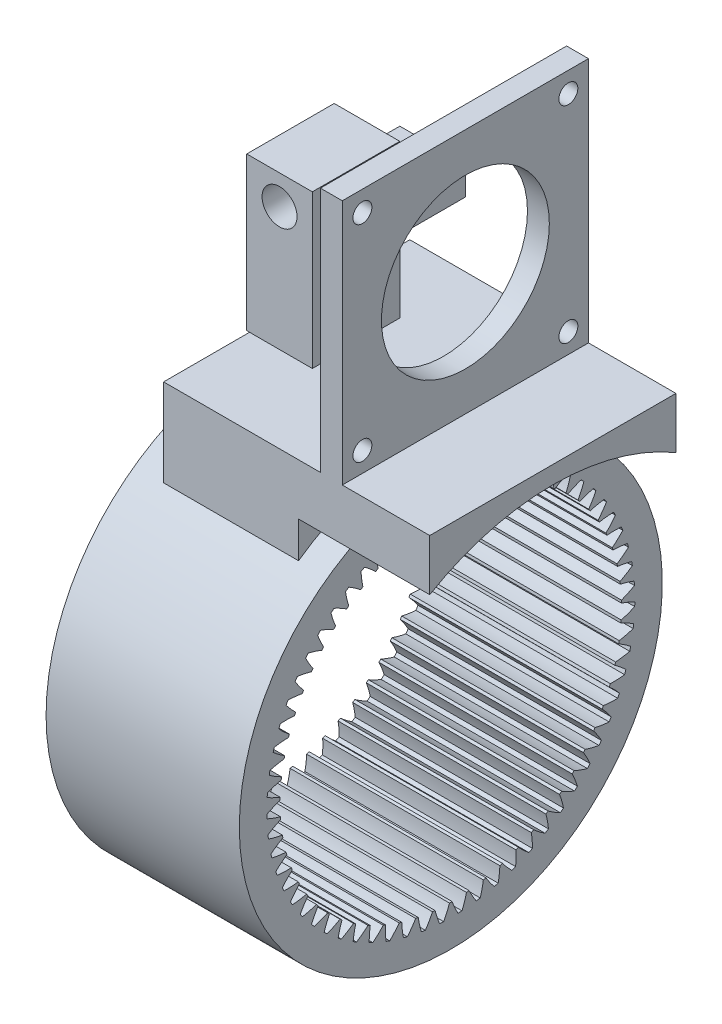
SolidWorks part; units mm, degrees
ref_plane "Plane1" through (0, 0, 0) normal (0, 0, 1) x (1, 0, 0)
ref_plane "Plane2" through (0, 0, 0) normal (0, 1, 0) x (1, 0, 0)
ref_plane "Plane3" through (0, 0, 0) normal (1, 0, 0) x (0, 0, -1)
sketch "HoldingSke" plane through (0, 0, 0) normal (0, 1, 0) x (1, 0, 0)
  line L0 (0, 0) -> (0.5, -0.866)
  line L1 (-15, 0) -> (100, 0) construction
  line L2 (0, 0) -> (-2.1039, 2.3779)
  line L3 (0, 0) -> (-11.863, 4.5341)
  line L4 (0, 0) -> (4.318, 7.479)
  line L5 (0, 0) -> (-23.7986, -8.8762)
  line L6 (0, 0) -> (-10.5278, -7.1032)
  line L7 (-2.1039, 2.3779) -> (3.3635, 27.1825)
  line L8 (-76.2, 3.3779) -> (-54.61, 3.3779)
  line L9 (-71.009, 38.7566) -> (-53.1078, 45.2721)
  line L10 (-76.2, 71.12) -> (104.1128, 71.12)
  line L11 (0, 0) -> (-12, 0)
  line L12 (-76.2, 101.6) -> (-76.162, 101.6)
  line L13 (24.9733, 27.94) -> (52.9518, 28.4284)
  line L14 (24.9733, 27.94) -> (24.9743, 27.94)
  line L15 (24.9733, 27.94) -> (100.4006, 29.5858)
  circle A0 centre (0, 0) radius 12.5
  circle A1 centre (0, 0) radius 12.7
  circle A2 centre (0, 0) radius 12.7
  dimension "MHD" = 25.4
  dimension "Hub_dia" = 25.4
  dimension "Diameter" = 25
  dimension "Num_teeth" = 60
  dimension "Pitch" = 1
  dimension "Overall_len" = 25.4
  dimension "Show_teeth" = 60
  dimension "Thickness" = 12.7
  dimension "OAL" = 25.4001
  dimension "T_dim" = 21.59
  dimension "Ap" = 20
  dimension "H" = 19.05
  dimension "Pitch_radius" = 180.3128
  dimension "Width" = 12
  dimension "Backlash" = 0.038
  dimension "Addendum_fac" = 1
  dimension "Dedendum_fac" = 1.25
  dimension "Clearance_fac" = 0.25
  dimension "Dedendum_add" = 0.001
  dimension "Module" = 1
sketch "BasProSke" plane through (0, 0, 0) normal (0, 1, 0) x (1, 0, 0)
  line L0 (-10, 0) -> (60, 0) construction
  line L1 (0, 29) -> (0, 31.2764)
  line L2 (0, 29) -> (32.815, 29)
  line L3 (32.815, 29) -> (32.815, 31.2764)
  line L4 (32.815, 31.2764) -> (0, 31.2764)
  dimension "Thickness" = 32.815
  dimension "Diameter" = 62.5528
  dimension "Inside_diameter" = 58
revolve "Base-Revolve" add sketch "BasProSke" angle 360 about L0
sketch "TooCutSke" plane through (0, 0, 0) normal (1, 0, 0) x (0, 0, -1)
  line L3 (0.8803, 29.9871) -> (0.8803, 53.6633) construction
  line L4 (0, 0) -> (0, 59.563) construction
  line L5 (0, 0) -> (-3.576, 68.2339) construction
  line L6 (-13.1633, 24.7167) -> (36.4631, 27.3175) construction
  circle A0 centre (0, 0) radius 30 construction
  circle A1 centre (0, 0) radius 31.251 construction
  circle A2 centre (0, 0) radius 25.3717 construction
  circle A3 centre (0, 0) radius 28.9746 construction
  arc A4 (1.2274, 28.9486) -> (0.3395, 31.2492) centre (-13.1633, 24.7167) ccw
  arc A5 (1.2274, 28.9486) -> (-1.2274, 28.9486) centre (0, 0) ccw
  arc A6 (0.3395, 31.2492) -> (-0.3395, 31.2492) centre (0, 0) ccw
  arc A7 (-0.3395, 31.2492) -> (-1.2274, 28.9486) centre (13.1633, 24.7167) ccw
  dimension "Pitch_dia" = 60
  dimension "Base_dia" = 50.7434
  dimension "Root_dia" = 62.502
  dimension "Overcut_dia" = 57.9492
  dimension "Flank_rad" = 15
  dimension "Half_ang" = 3
  dimension "Half_CT" = 0.8803
extrude "ToothCut" cut sketch "TooCutSke" along normal through all
fillet "Breaks" [suppressed] radius 0.1
fillet "RootFillets" [suppressed] radius 0.251
pattern_circular "TeethCuts" count 63 over 360 about axis through (-10, 0, 0) along (1, 0, 0) of "ToothCut"
scale "Scale1" scale about centroid uniform scaling yes scale factor 2
sketch "Sketch1" plane through (49.2225, 0, 0) normal (1, 0, 0) x (0, 0, -1)
  circle A0 centre (0, 0) radius 62.5528
sketch "Sketch2" plane through (49.2225, 0, 0) normal (1, 0, 0) x (0, 0, -1)
  circle A0 centre (0, 0) radius 72.5528
  circle A1 centre (0, 0) radius 62.5528
extrude "Boss-Extrude1" add sketch "Sketch2" against normal blind 65.63
scale "Scale2" scale about centroid uniform scaling yes scale factor 1.1
scale "Scale3" scale about centroid uniform scaling yes scale factor 1.01
scale "Scale4" scale about centroid uniform scaling yes scale factor 0.990099
scale "Scale5" scale about centroid uniform scaling yes scale factor 0.909091
scale "Scale6" scale about centroid uniform scaling yes scale factor 1.01
sketch "Sketch3" plane through (-16.7356, 0, 0) normal (-1, 0, 0) x (0, 0, 1)
  circle A0 centre (0, 0) radius 72.5528
  circle A1 centre (0, 0) radius 73.2783
extrude "Cut-Extrude1" cut sketch "Sketch3" against normal through all
ref_plane "Plane4" through (39.5507, 0, 0) normal (1, 0, 0) x (0, 0, -1)
sketch "Sketch4" plane through (39.5507, 0, 0) normal (1, 0, 0) x (0, 0, -1)
  line L10 (-42.225, 88.9996) -> (-42.225, 58.9996)
  line L11 (42.225, 88.9996) -> (42.225, 58.9996)
  line L12 (0, 0) -> (-42.225, 58.9996) construction
  line L13 (42.225, 58.9996) -> (0, 0) construction
  line L18 (42.225, 88.9996) -> (-42.225, 88.9996)
  arc A0 (42.225, 58.9996) -> (-42.225, 58.9996) centre (0, 0) ccw
  circle A1 centre (0, 0) radius 72.5528 construction
  point P12 (0, 72.5528)
  dimension "D1" = 84.45
  dimension "D3" = 30
extrude "Boss-Extrude2" add sketch "Sketch4" against normal blind 46.2863
scale "Scale7" scale about centroid uniform scaling yes scale factor 0.666667
sketch "Sketch17" plane through (31.8363, 0, 0) normal (1, 0, 0) x (0, 0, -1)
  line L1 (-28.15, 64.6246) -> (-28.15, 44.6246) construction
  line L4 (-28.15, 52.8966) -> (-28.15, 64.6246)
  line L5 (-28.15, 64.6246) -> (28.15, 64.6246)
  line L6 (28.15, 64.6246) -> (28.15, 52.8966)
  arc A1 (28.15, 52.8966) -> (-28.15, 52.8966) centre (0, 5.2915) ccw
  circle A2 centre (0, 5.2915) radius 48.3685 construction
  dimension "D1" = 110.6104
extrude "Boss-Extrude3" add sketch "Sketch17" along normal blind 30
ref_plane "Plane5" through (16.4075, 0, 0) normal (1, 0, 0) x (0, 0, -1)
ref_plane "Plane6" through (41.8363, 0, 0) normal (1, 0, 0) x (0, 0, -1)
sketch "Sketch18" plane through (41.8363, 0, 0) normal (1, 0, 0) x (0, 0, -1)
  line L0 (28.15, 52.8966) -> (28.15, 64.6246) construction
  line L1 (-28.15, 64.6246) -> (28.15, 64.6246)
  line L2 (-28.15, 64.6246) -> (-28.15, 120.9246)
  line L3 (-28.15, 120.9246) -> (28.15, 120.9246)
  line L4 (28.15, 64.6246) -> (28.15, 120.9246)
  line L6 (23.55, 69.1773) -> (-23.55, 69.1773) construction
  line L7 (23.55, 69.1773) -> (23.55, 116.2773) construction
  line L8 (23.55, 116.2773) -> (-23.55, 116.2773) construction
  line L9 (-23.55, 69.1773) -> (-23.55, 116.2773) construction
  line L10 (23.55, 69.1773) -> (-23.55, 116.2773) construction
  line L11 (23.55, 116.2773) -> (-23.55, 69.1773) construction
  circle A1 centre (-23.55, 116.2773) radius 2.165
  circle A2 centre (23.55, 116.2773) radius 2.165
  circle A3 centre (-23.55, 69.1773) radius 2.165
  circle A4 centre (23.55, 69.1773) radius 2.165
  circle A5 centre (0, 92.7273) radius 19.2
  dimension "D2" = 38.4
  dimension "D1" = 56.3
  dimension "D4" = 47.1
  dimension "D5" = 47.1
extrude "Boss-Extrude4" add sketch "Sketch18" against normal blind 5
ref_plane "Plane7" through (0, 0, -1.5) normal (0, 0, 1) x (1, 0, 0)
sketch "Sketch19" plane through (0, 0, -1.5) normal (0, 0, 1) x (1, 0, 0)
  line L0 (36.8363, 64.6246) -> (7.8363, 64.6246) construction
  line L1 (0.9787, 64.6246) -> (36.8363, 64.6246) construction
  line L2 (7.8363, 64.6246) -> (7.8363, 92.9185) construction
  line L4 (0.3363, 99.6246) -> (15.3363, 99.6246)
  line L5 (0.3363, 99.6246) -> (0.3363, 64.6246)
  line L6 (0.3363, 64.6246) -> (15.3363, 64.6246)
  line L7 (15.3363, 99.6246) -> (15.3363, 64.6246)
  line L8 (0.3363, 99.6246) -> (15.3363, 64.6246) construction
  line L9 (0.3363, 64.6246) -> (15.3363, 99.6246) construction
  circle A0 centre (7.8363, 92.9185) radius 4
  point P5 (7.8363, 82.1246)
  dimension "D5" = 8
  dimension "D1" = 29
  dimension "D2" = 28.2939
  dimension "D3" = 15
  dimension "D4" = 35
extrude "Boss-Extrude5" add sketch "Sketch19" along normal mid plane 20
sketch "Sketch20" plane through (0.3363, 0, 0) normal (-1, 0, 0) x (0, 0, 1)
  line L0 (-11.5, 99.6246) -> (-11.5, 64.6246) construction
  line L1 (-11.5, 87.6246) -> (-26.5, 87.6246)
  line L2 (-11.5, 87.6246) -> (-11.5, 81.0824)
  line L3 (-11.5, 81.0824) -> (-26.5, 81.0824)
  line L4 (-26.5, 87.6246) -> (-26.5, 81.0824)
  dimension "D1" = 12
  dimension "D2" = 15
extrude "Boss-Extrude6" add sketch "Sketch20" against normal blind 15 separate body
sketch "Sketch21" plane through (0, 87.6246, 0) normal (0, 1, 0) x (1, 0, 0)
  line L0 (15.3363, 26.5) -> (0.3363, 11.5) construction
  line L1 (15.3363, 11.5) -> (15.3363, 26.5) construction
  line L2 (15.3363, 26.5) -> (0.3363, 26.5) construction
  line L3 (15.3363, 11.5) -> (0.3363, 26.5) construction
  circle A0 centre (7.8363, 19) radius 2.165
extrude "Cut-Extrude2" cut sketch "Sketch21" against normal up to next (6.5422 mm away)
sketch "Sketch22" plane through (0, 81.0824, 0) normal (0, -1, 0) x (1, 0, 0)
  line L1 (6.261, -22.7093) -> (10.261, -22.2189)
  line L2 (10.261, -22.2189) -> (11.8363, -18.5095)
  line L3 (11.8363, -18.5095) -> (9.4115, -15.2907)
  line L4 (9.4115, -15.2907) -> (5.4115, -15.7811)
  line L5 (5.4115, -15.7811) -> (3.8363, -19.4905)
  line L6 (3.8363, -19.4905) -> (6.261, -22.7093)
  circle A0 centre (7.8363, -19) radius 3.49 construction
  dimension "D1" = 4
extrude "Cut-Extrude3" cut sketch "Sketch22" against normal blind 3
equation "' \"Module@HoldingSke\" = 6.35"
equation "' \"Num_teeth@HoldingSke\" = 24"
equation "' \"Ap@HoldingSke\" =  14.5"
equation "' \"Ap@HoldingSke\" = 14.5"
equation "' \"Width@HoldingSke\" = 12"
equation "' \"Diameter@HoldingSke\" = 8 * 25.4"
equation "' \"Show_teeth@HoldingSke\" = 100"
equation "' \"Backlash@HoldingSke\" = 0.009 * 25.4"
equation "' \"Addendum_fac@HoldingSke\" = 1.0"
equation "' \"Dedendum_fac@HoldingSke\" = 1.25"
equation "' \"Dedendum_add@HoldingSke\" = 0.00005 * 25.4"
equation "' \"Clearance_fac@HoldingSke\" = 0.25"
equation "\"Pitch@HoldingSke\" = 1 / \"Module@HoldingSke\" "
equation "\"Overcut_dia@TooCutSke\" = (\"Num_teeth@HoldingSke\" - 2 * \"Addendum_fac@HoldingSke\") / \"Pitch@HoldingSke\" - 0.002 * 25.4"
equation "\"Pitch_dia@TooCutSke\" = \"Num_teeth@HoldingSke\" / \"Pitch@HoldingSke\""
equation "\"Base_dia@TooCutSke\" = \"Num_teeth@HoldingSke\" / \"Pitch@HoldingSke\" * cos((\"Ap@HoldingSke\"  * 3.14159265 / 180)) * 0.90"
equation "\"Root_dia@TooCutSke\" = \"Num_teeth@HoldingSke\"  / \"Pitch@HoldingSke\" + 2 *  \"Dedendum_fac@HoldingSke\"/ \"Pitch@HoldingSke\" + \"Dedendum_add@HoldingSke\" * 2"
equation "\"Half_ang@TooCutSke\" = 180 / \"Num_teeth@HoldingSke\""
equation "\"Half_CT@TooCutSke\" = \"Num_teeth@HoldingSke\" / \"Pitch@HoldingSke\" * sin((3.14159265 / 2 / \"Num_teeth@HoldingSke\")) / 2 + 10 * \"Backlash@HoldingSke\" / 4"
equation "\"Flank_rad@TooCutSke\" = \"Num_teeth@HoldingSke\" / \"Pitch@HoldingSke\" / 4"
equation "\"Radius@RootFillets\"= \"Clearance_fac@HoldingSke\" / \"Pitch@HoldingSke\" + \"Dedendum_add@HoldingSke\""
equation "\"Break_rad@Breaks\" = 0.02 / \"Pitch@HoldingSke\" * 5"
equation "\"Diameter@BasProSke\" = \"Num_teeth@HoldingSke\"  / \"Pitch@HoldingSke\" + 2 *  \"Dedendum_fac@HoldingSke\"/ \"Pitch@HoldingSke\" + \"Dedendum_add@HoldingSke\" * 2 + 0.002 * 25.4"
equation "\"Diameter@BasProSke\" = ((sgn( \"Diameter@BasProSke\"  - \"Diameter@HoldingSke\" )+1)*( \"Diameter@BasProSke\"  - \"Diameter@HoldingSke\" ))/2 + \"Diameter@HoldingSke\""
equation "\"Inside_diameter@BasProSke\" =  (\"Num_teeth@HoldingSke\" - 2 * \"Addendum_fac@HoldingSke\") / \"Pitch@HoldingSke\" "
